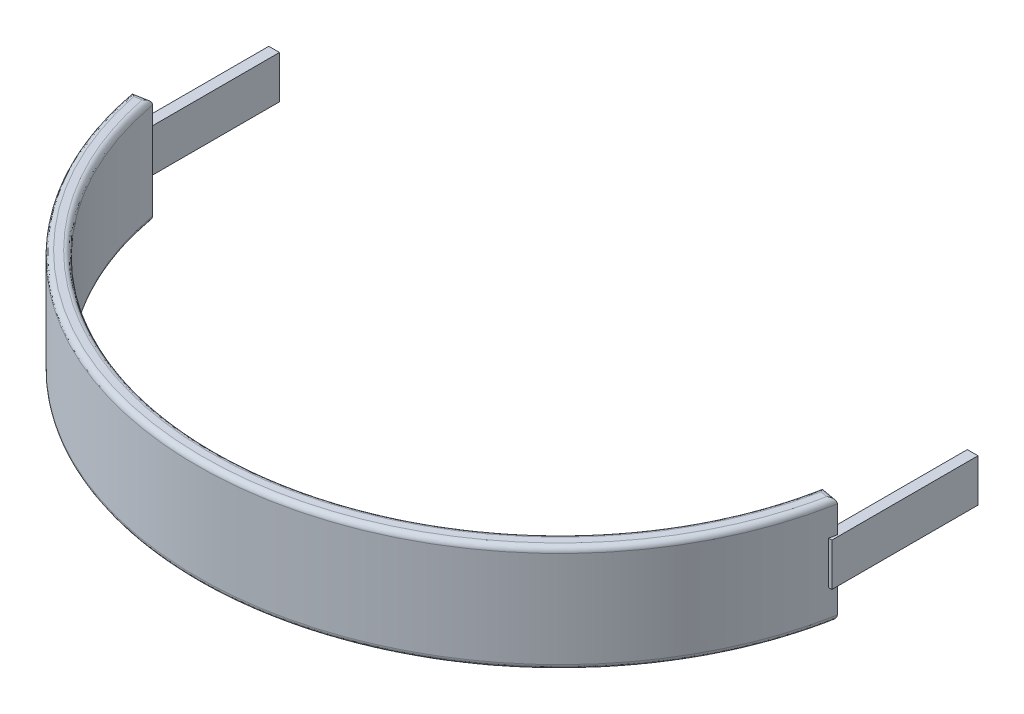
SolidWorks part; units mm, degrees
ref_plane "Front Plane" through (0, 0, 0) normal (1, 0, 0) x (0, 1, 0)
ref_plane "Top Plane" through (0, 0, 0) normal (0, 0, 1) x (0, 1, 0)
ref_plane "Right Plane" through (0, 0, 0) normal (0, 1, 0) x (-1, 0, 0)
sketch "Sketch1" plane through (0, 0, 0) normal (0, 1, 0) x (-1, 0, 0)
  line L0 (98.9708, -78.056) -> (94.0515, -78.9508)
  line L1 (-94.0515, -78.9508) -> (-98.9708, -78.056)
  spline S0 degree 3 poles (-98.9708, -78.056) (-98.2926, -74.3265) (-96.9384, -68.7911) (-94.4826, -61.6075) (-92.3199, -56.3309) (-89.8447, -51.1858) (-87.0653, -46.1895) (-83.9914, -41.359) (-80.6335, -36.7106) (-77.0028, -32.26) (-73.112, -28.0221) (-68.9742, -24.0114) (-64.6034, -20.2412) (-60.0146, -16.7242) (-55.2232, -13.4723) (-50.2456, -10.4963) (-45.0985, -7.8063) (-39.7994, -5.4112) (-34.3662, -3.319) (-28.8172, -1.5367) (-23.1711, -0.0703) (-17.4469, 1.0754) (-11.664, 1.8964) (-5.8418, 2.3902) (0, 2.5549) (5.8418, 2.3902) (11.664, 1.8964) (17.4469, 1.0754) (23.1711, -0.0703) (28.8172, -1.5367) (34.3662, -3.319) (39.7994, -5.4112) (45.0985, -7.8063) (50.2456, -10.4963) (55.2232, -13.4723) (60.0146, -16.7242) (64.6034, -20.2412) (68.9742, -24.0114) (73.112, -28.0221) (77.0028, -32.26) (80.6335, -36.7106) (83.9914, -41.359) (87.0653, -46.1895) (89.8447, -51.1858) (92.3199, -56.3309) (94.4826, -61.6075) (96.9384, -68.7911) (98.2926, -74.3265) (98.9708, -78.056) knots 0 0 0 0 0.041059 0.061616 0.082195 0.1028 0.123433 0.144096 0.164791 0.185519 0.206282 0.22708 0.247912 0.268778 0.289678 0.310609 0.33157 0.352559 0.373573 0.394609 0.415664 0.436734 0.457816 0.478906 0.5 0.521094 0.542184 0.563266 0.584336 0.605391 0.626427 0.647441 0.66843 0.689391 0.710322 0.731222 0.752088 0.77292 0.793718 0.814481 0.835209 0.855904 0.876567 0.8972 0.917805 0.938384 0.958941 1 1 1 1
  spline S1 degree 3 poles (94.0515, -78.9508) (93.409, -75.4174) (92.1259, -70.1727) (89.7988, -63.3658) (87.749, -58.3646) (85.4024, -53.4869) (82.7669, -48.7493) (79.8513, -44.1676) (76.6655, -39.7575) (73.22, -35.5339) (69.5266, -31.5111) (65.5976, -27.7028) (61.4463, -24.122) (57.0867, -20.7807) (52.5335, -17.6905) (47.8021, -14.8617) (42.9085, -12.3042) (37.8693, -10.0265) (32.7015, -8.0366) (27.4227, -6.3411) (22.0508, -4.9459) (16.6039, -3.8558) (11.1007, -3.0744) (5.5598, -2.6045) (0, -2.4477) (-5.5598, -2.6045) (-11.1007, -3.0744) (-16.6039, -3.8558) (-22.0508, -4.9459) (-27.4227, -6.3411) (-32.7015, -8.0366) (-37.8693, -10.0265) (-42.9085, -12.3042) (-47.8021, -14.8617) (-52.5335, -17.6905) (-57.0867, -20.7807) (-61.4463, -24.122) (-65.5976, -27.7028) (-69.5266, -31.5111) (-73.22, -35.5339) (-76.6655, -39.7575) (-79.8513, -44.1676) (-82.7669, -48.7493) (-85.4024, -53.4869) (-87.749, -58.3646) (-89.7988, -63.3658) (-92.1259, -70.1727) (-93.409, -75.4174) (-94.0515, -78.9508) knots 0 0 0 0 0.040956 0.061466 0.082003 0.102569 0.123169 0.143803 0.164476 0.185187 0.205938 0.22673 0.247563 0.268435 0.289346 0.310294 0.331277 0.352292 0.373336 0.394405 0.415497 0.436607 0.45773 0.478863 0.5 0.521137 0.54227 0.563393 0.584503 0.605595 0.626664 0.647708 0.668723 0.689706 0.710654 0.731565 0.752437 0.77327 0.794062 0.814813 0.835524 0.856197 0.876831 0.897431 0.917997 0.938534 0.959044 1 1 1 1
extrude "Shell" add sketch "Sketch1" along normal mid plane 30
fillet "ShellFillet" radius 1.5 8 edges at (96.5112, -15, -78.5034) (-96.5112, -15, -78.5034) (-96.5112, 15, -78.5034) (96.5112, 15, -78.5034)
ref_plane "Plane_x_-98p0" through (-98, 0, 0) normal (1, 0, 0) x (0, 1, 0)
sketch "Sketch2" plane through (-98, 0, 0) normal (1, 0, 0) x (0, 1, 0)
  line L0 (-6, -117) -> (6, -117)
  line L1 (6, -117) -> (6, -76)
  line L2 (6, -76) -> (-6, -76)
  line L3 (-6, -76) -> (-6, -117)
extrude "SliderL" add sketch "Sketch2" along normal mid plane 3
ref_plane "Plane_x_+98p0" through (98, 0, 0) normal (1, 0, 0) x (0, 1, 0)
sketch "Sketch3" plane through (98, 0, 0) normal (1, 0, 0) x (0, 1, 0)
  line L0 (-6, -117) -> (6, -117)
  line L1 (6, -117) -> (6, -76)
  line L2 (6, -76) -> (-6, -76)
  line L3 (-6, -76) -> (-6, -117)
extrude "SliderR" add sketch "Sketch3" along normal mid plane 3
sketch "Sketch4" plane through (0, 0, 0) normal (0, 1, 0) x (-1, 0, 0)
  line L0 (0, -130) -> (-130, -130)
  line L1 (-130, -130) -> (-130, 10)
  line L2 (-130, 10) -> (0, 10)
  line L3 (0, 10) -> (0, -130)
extrude "CutL" [suppressed] cut sketch "Sketch4" against normal mid plane 60
sketch "Sketch5" plane through (0, 0, 0) normal (0, 1, 0) x (-1, 0, 0)
  line L0 (0, -130) -> (130, -130)
  line L1 (130, -130) -> (130, 10)
  line L2 (130, 10) -> (0, 10)
  line L3 (0, 10) -> (0, -130)
extrude "CutR" [suppressed] cut sketch "Sketch5" against normal mid plane 60
